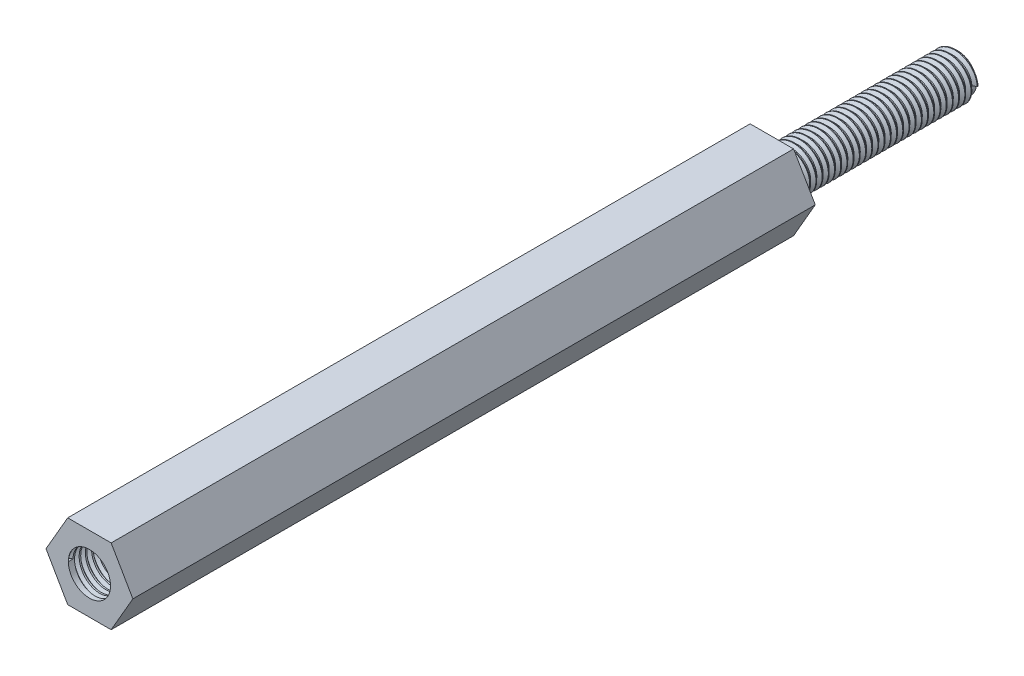
SolidWorks part; units mm, degrees
material "1.7036 (28CrS4)"
ref_plane "Plan de face" through (0, 0, 0) normal (0, 0, 1) x (1, 0, 0)
ref_plane "Plan de dessus" through (0, 0, 0) normal (0, 1, 0) x (1, 0, 0)
ref_plane "Plan de droite" through (0, 0, 0) normal (1, 0, 0) x (0, 0, -1)
sketch "Esquisse1" plane through (0, 0, 0) normal (0, 0, 1) x (1, 0, 0)
  line L0 (0, 3.5) -> (7, 3.5) construction
  line L1 (0, 0) -> (7, 0) construction
  line L2 (0, 0) -> (0, 7) construction
  line L3 (0, 7) -> (7, 7) construction
  line L4 (7, 0) -> (7, 7) construction
  line L5 (3.5, 7) -> (3.5, 0) construction
  line L7 (5.25, 0.4689) -> (7, 3.5)
  line L8 (7, 3.5) -> (5.25, 6.5311)
  line L9 (5.25, 6.5311) -> (1.75, 6.5311)
  line L10 (1.75, 6.5311) -> (0, 3.5)
  line L11 (0, 3.5) -> (1.75, 0.4689)
  line L12 (1.75, 0.4689) -> (5.25, 0.4689)
  circle A0 centre (3.5, 3.5) radius 3.5 construction
  dimension "D3" = 7
  dimension "D1" = 7
  dimension "D2" = 7
extrude "Boss.-Extru.1" add sketch "Esquisse1" along normal blind 70
sketch "Esquisse2" plane through (0, 0, 70) normal (0, 0, 1) x (1, 0, 0)
  line L0 (3.5, 6.5311) -> (3.5, 0.4689) construction
  line L1 (0.875, 1.9845) -> (6.125, 5.0155) construction
  line L6 (1.75, 0.4689) -> (5.25, 0.4689)
  line L7 (5.25, 0.4689) -> (7, 3.5)
  line L8 (7, 3.5) -> (5.25, 6.5311)
  line L9 (5.25, 6.5311) -> (1.75, 6.5311)
  line L10 (1.75, 6.5311) -> (0, 3.5)
  line L11 (0, 3.5) -> (1.75, 0.4689)
  line L12 (1.75, 0.4689) -> (5.25, 0.4689)
  line L13 (5.25, 0.4689) -> (7, 3.5)
  line L14 (7, 3.5) -> (5.25, 6.5311)
  line L15 (5.25, 6.5311) -> (1.75, 6.5311)
  line L16 (1.75, 6.5311) -> (0, 3.5)
  line L17 (0, 3.5) -> (1.75, 0.4689)
  circle A0 centre (3.5, 3.5) radius 1.5
  dimension "D2" = 3
  dimension "D1" = 0
hole_wizard "Dégagement M31" positions "Esquisse6" profile "Esquisse7" hole size "M3" standard "ISO"
sketch "Esquisse6" plane through (0, 0, 70) normal (0, 0, 1) x (1, 0, 0)
  point P0 (3.5, 3.5)
sketch "Esquisse7" plane through (3.5, 3.5, 70) normal (1, 0, 0) x (0, -1, 0)
  line L0 (0, 0) -> (0, 9.0215)
  line L1 (0, 9.0215) -> (1.7, 8)
  line L2 (1.7, 8) -> (1.7, 0)
  line L5 (1.7, 0) -> (0, 0)
  line L10 (0, 9.0215) -> (-1.7, 8) construction
  line L11 (0, -6.35) -> (0, 107.95) construction
  dimension "Diamètre du perçage" = 3.4
  dimension "Profondeur du perçage" = 8
  dimension "Angle de pointe" = 118
thread "Filetage1" pitch 0.5 start angle 0, offset 0, length 10, pitch 0.5, diameter 3.4
ref_plane "Plan1" through (1.8, 3.5, 70) normal (0, -1, 0) x (-1, 0, 0)
sketch "Profil de filetage1" plane through (1.8, 3.5, 70) normal (0, -1, 0) x (-1, 0, 0)
  line L0 (0, 0) -> (0, 0.5) construction
  line L1 (0, 0) -> (0.2706, 0.1562)
  line L2 (0.2706, 0.1562) -> (0.2706, 0.2187)
  line L3 (0.2706, 0.2187) -> (0, 0.375)
  line L4 (0.2706, 0.1875) -> (0, 0.1875) construction
  line L11 (0, 0) -> (0, 0.375)
  point P2 (0, 0)
  dimension "Pitch" = 0.5
  dimension "Profile_Angle" = 60
  dimension "Profile_Land" = 0.0625
  dimension "Profile_Height" = 0.2706
hole_wizard "Dégagement M32" [suppressed] positions "Esquisse10" profile "Esquisse11" hole size "M3" standard "ISO"
sketch "Esquisse10" plane through (0, 0, 0) normal (0, 0, -1) x (-1, 0, 0)
  point P0 (-3.5, 3.5)
sketch "Esquisse11" plane through (3.5, 3.5, 0) normal (1, 0, 0) x (0, 1, 0)
  line L0 (0, 0) -> (0, 9.0215)
  line L1 (0, 9.0215) -> (1.7, 8)
  line L2 (1.7, 8) -> (1.7, 0)
  line L5 (1.7, 0) -> (0, 0)
  line L10 (0, 9.0215) -> (-1.7, 8) construction
  line L11 (0, -6.35) -> (0, 107.95) construction
  dimension "Diamètre du perçage" = 3.4
  dimension "Profondeur du perçage" = 8
  dimension "Angle de pointe" = 118
sketch "Esquisse12" plane through (0, 0, 0) normal (0, 0, -1) x (-1, 0, 0)
  line L6 (-5.25, 0.4689) -> (-1.75, 0.4689)
  line L7 (-1.75, 0.4689) -> (0, 3.5)
  line L8 (0, 3.5) -> (-1.75, 6.5311)
  line L9 (-1.75, 6.5311) -> (-5.25, 6.5311)
  line L10 (-5.25, 6.5311) -> (-7, 3.5)
  line L11 (-7, 3.5) -> (-5.25, 0.4689)
  line L12 (-5.25, 0.4689) -> (-1.75, 0.4689)
  line L13 (-1.75, 0.4689) -> (0, 3.5)
  line L14 (0, 3.5) -> (-1.75, 6.5311)
  line L15 (-1.75, 6.5311) -> (-5.25, 6.5311)
  line L16 (-5.25, 6.5311) -> (-7, 3.5)
  line L17 (-7, 3.5) -> (-5.25, 0.4689)
  circle A0 centre (-3.5, 3.5) radius 1.5
  dimension "D2" = 3
  dimension "D1" = 0
extrude "Enlèv. mat.-Extru.1" cut sketch "Esquisse12" against normal blind 15
thread "Filetage2" pitch 0.5 profile "Profil de filetage2" start angle 0, offset 0, length 15, pitch 0.5, diameter 3
ref_plane "Plan2" through (5, 3.5, 0) normal (0, -1, 0) x (1, 0, 0)
sketch "Profil de filetage2" plane through (5, 3.5, 0) normal (0, -1, 0) x (1, 0, 0)
  line L0 (0, 0) -> (0, 0.5) construction
  line L1 (0, 0) -> (0.2706, 0.1562)
  line L2 (0.2706, 0.1562) -> (0.2706, 0.2187)
  line L3 (0.2706, 0.2187) -> (0, 0.375)
  line L4 (0.2706, 0.1875) -> (0, 0.1875) construction
  line L11 (0, 0) -> (0, 0.375)
  point P2 (0, 0)
  dimension "Pitch" = 0.5
  dimension "Profile_Angle" = 60
  dimension "Profile_Land" = 0.0625
  dimension "Profile_Height" = 0.2706
equation "\"diam_cercle_circons\"= 7"
equation "\"D1@Esquisse1\"=\"diam_cercle_circons\""
equation "\"D2@Esquisse1\"=\"diam_cercle_circons\""
equation "\"Hauteur\"= 70"
equation "\"D1@Boss.-Extru.1\"=\"Hauteur\""
equation "\"D3@Esquisse1\"=\"diam_cercle_circons\""
